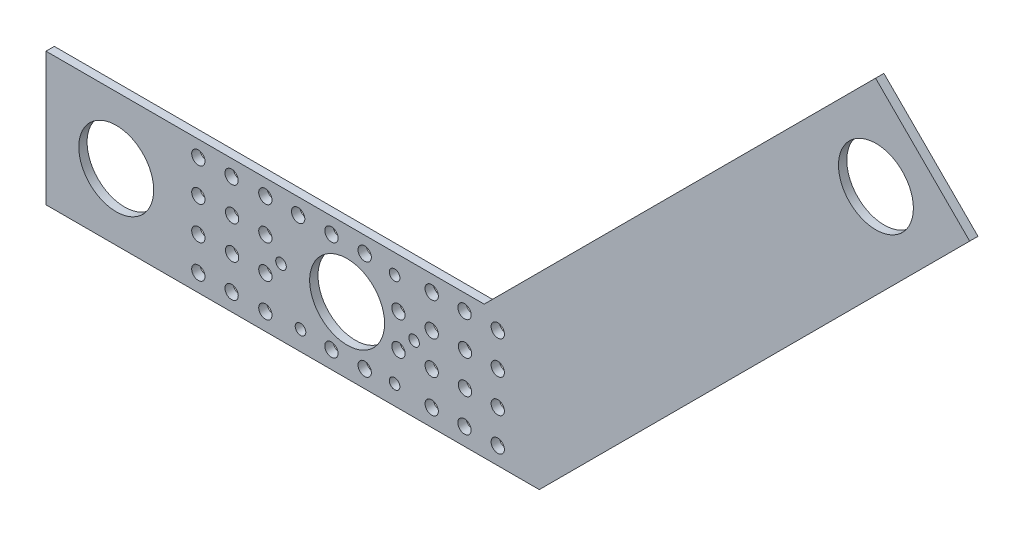
SolidWorks part; units mm, degrees
ref_plane "Front Plane" through (0, 0, 0) normal (0, 0, 1) x (1, 0, 0)
ref_plane "Top Plane" through (0, 0, 0) normal (0, 1, 0) x (1, 0, 0)
ref_plane "Right Plane" through (0, 0, 0) normal (1, 0, 0) x (0, 0, -1)
sketch "Sketch1" plane through (0, 0, 0) normal (0, 0, 1) x (1, 0, 0)
  line L0 (-59.6938, 4.2713) -> (-59.6938, -46.5287)
  line L1 (-59.6938, -46.5287) -> (128.6141, -46.5287)
  line L2 (128.6141, -46.5287) -> (292.9114, 117.7686)
  line L3 (292.9114, 117.7686) -> (256.9904, 153.6896)
  line L4 (256.9904, 153.6896) -> (107.5721, 4.2713)
  line L5 (107.5721, 4.2713) -> (-59.6938, 4.2713)
  circle A0 centre (24.0402, -14.5121) radius 2.54 construction
  circle A1 centre (74.8402, -14.5121) radius 2.54 construction
  circle A2 centre (87.5402, -14.5121) radius 2.54 construction
  circle A3 centre (100.2402, -14.5121) radius 2.54 construction
  circle A4 centre (100.2402, -27.2121) radius 2.54 construction
  circle A5 centre (87.5402, -27.2121) radius 2.54 construction
  circle A6 centre (74.8402, -27.2121) radius 2.54 construction
  circle A7 centre (24.0402, -27.2121) radius 2.54 construction
  circle A8 centre (11.3402, -27.2121) radius 2.54 construction
  circle A9 centre (11.3402, -14.5121) radius 2.54 construction
  circle A10 centre (11.1589, -1.8121) radius 2.54 construction
  circle A11 centre (24.0402, -1.8121) radius 2.54 construction
  circle A12 centre (36.5589, -1.8121) radius 2.54 construction
  circle A13 centre (49.2589, -1.8121) radius 2.54 construction
  circle A14 centre (61.9589, -1.8121) radius 2.54 construction
  circle A15 centre (87.5402, -1.8121) radius 2.54 construction
  circle A16 centre (100.0589, -1.8121) radius 2.54 construction
  circle A17 centre (112.7589, -1.8121) radius 2.54 construction
  circle A18 centre (112.7589, -14.5121) radius 2.54 construction
  circle A19 centre (112.7589, -27.2121) radius 2.54 construction
  circle A20 centre (112.7589, -39.9121) radius 2.54 construction
  circle A21 centre (100.0589, -39.9121) radius 2.54 construction
  circle A22 centre (87.5402, -39.9121) radius 2.54 construction
  circle A23 centre (61.9589, -39.9121) radius 2.54 construction
  circle A24 centre (49.2589, -39.9121) radius 2.54 construction
  circle A25 centre (24.0402, -39.9121) radius 2.54 construction
  circle A26 centre (11.1589, -39.9121) radius 2.54 construction
  circle A27 centre (-1.5411, -39.9121) radius 2.54 construction
  circle A28 centre (-1.5411, -27.2121) radius 2.54 construction
  circle A29 centre (-1.5411, -14.5121) radius 2.54 construction
  circle A30 centre (-1.5411, -1.8121) radius 2.54 construction
  circle A31 centre (73.3783, -3.1782) radius 2.0193 construction
  circle A32 centre (80.8178, -21.1387) radius 2.0193 construction
  circle A33 centre (73.3783, -39.0992) radius 2.0193 construction
  circle A34 centre (37.4573, -39.0992) radius 2.0193 construction
  circle A35 centre (30.0178, -21.1387) radius 2.0193 construction
  circle A36 centre (55.2538, -21.1287) radius 14.3002 construction
  circle A37 centre (-32.8842, -21.1287) radius 14.3002 construction
  circle A38 centre (24.0402, -14.5121) radius 2.54
  circle A39 centre (74.8402, -14.5121) radius 2.54
  circle A40 centre (87.5402, -14.5121) radius 2.54
  circle A41 centre (100.2402, -14.5121) radius 2.54
  circle A42 centre (100.2402, -27.2121) radius 2.54
  circle A43 centre (87.5402, -27.2121) radius 2.54
  circle A44 centre (74.8402, -27.2121) radius 2.54
  circle A45 centre (24.0402, -27.2121) radius 2.54
  circle A46 centre (11.3402, -27.2121) radius 2.54
  circle A47 centre (11.3402, -14.5121) radius 2.54
  circle A48 centre (11.1589, -1.8121) radius 2.54
  circle A49 centre (24.0402, -1.8121) radius 2.54
  circle A50 centre (36.5589, -1.8121) radius 2.54
  circle A51 centre (49.2589, -1.8121) radius 2.54
  circle A52 centre (61.9589, -1.8121) radius 2.54
  circle A53 centre (87.5402, -1.8121) radius 2.54
  circle A54 centre (100.0589, -1.8121) radius 2.54
  circle A55 centre (112.7589, -1.8121) radius 2.54
  circle A56 centre (112.7589, -14.5121) radius 2.54
  circle A57 centre (112.7589, -27.2121) radius 2.54
  circle A58 centre (112.7589, -39.9121) radius 2.54
  circle A59 centre (100.0589, -39.9121) radius 2.54
  circle A60 centre (87.5402, -39.9121) radius 2.54
  circle A61 centre (61.9589, -39.9121) radius 2.54
  circle A62 centre (49.2589, -39.9121) radius 2.54
  circle A63 centre (24.0402, -39.9121) radius 2.54
  circle A64 centre (11.1589, -39.9121) radius 2.54
  circle A65 centre (-1.5411, -39.9121) radius 2.54
  circle A66 centre (-1.5411, -27.2121) radius 2.54
  circle A67 centre (-1.5411, -14.5121) radius 2.54
  circle A68 centre (-1.5411, -1.8121) radius 2.54
  circle A69 centre (73.3783, -3.1782) radius 2.0193
  circle A70 centre (80.8178, -21.1387) radius 2.0193
  circle A71 centre (73.3783, -39.0992) radius 2.0193
  circle A72 centre (37.4573, -39.0992) radius 2.0193
  circle A73 centre (30.0178, -21.1387) radius 2.0193
  circle A74 centre (55.2538, -21.1287) radius 14.3002
  circle A75 centre (-32.8842, -21.1287) radius 14.3002
  circle A76 centre (257.1207, 117.8989) radius 14.3002
  point P122 (107.5721, 4.2713)
  dimension "D4" = 245.11
  dimension "D1" = 50.8
  dimension "D2" = 50.8
  dimension "D3" = 135
  dimension "D5" = 25.4
extrude "Boss-Extrude1" add sketch "Sketch1" along normal blind 3.175
